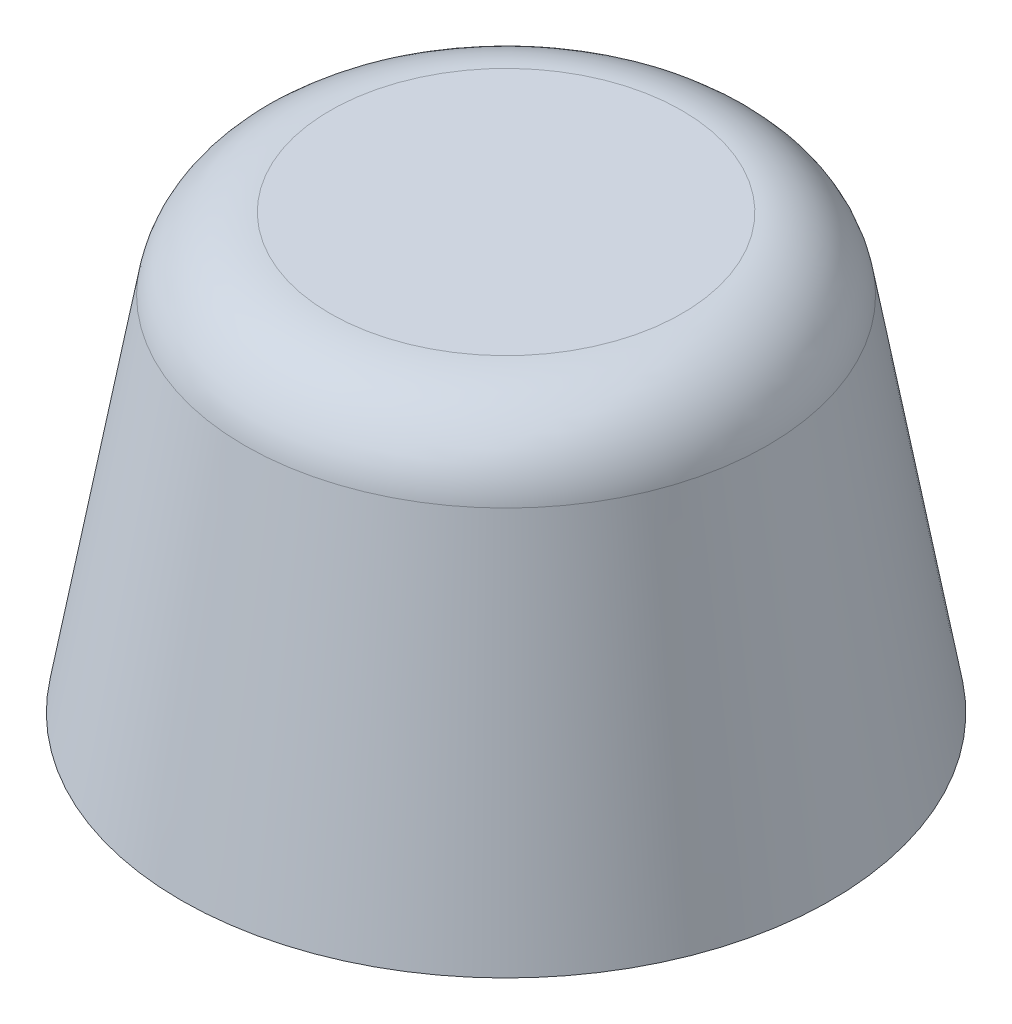
SolidWorks part; units mm, degrees
ref_plane "Front Plane" through (0, 0, 0) normal (0, 0, 1) x (1, 0, 0)
ref_plane "Top Plane" through (0, 0, 0) normal (0, 1, 0) x (1, 0, 0)
ref_plane "Right Plane" through (0, 0, 0) normal (1, 0, 0) x (0, 0, -1)
sketch "Sketch1" plane through (0, 0, 0) normal (0, 1, 0) x (1, 0, 0)
  circle A0 centre (0, 0) radius 7.5
extrude "Boss-Extrude1" add sketch "Sketch1" along normal blind 10 draft 10
sketch "Sketch2" plane through (0, 0, 0) normal (0, -1, 0) x (1, 0, 0)
  circle A0 centre (0, 0) radius 5.625
extrude "Cut-Extrude1" cut sketch "Sketch2" against normal blind 2.25
fillet "Fillet1" radius 2 1 edges at (0, 10, 5.7367)
shell "Shell2" thickness 1.5 removed face at (0, 2.25, -5.625)
